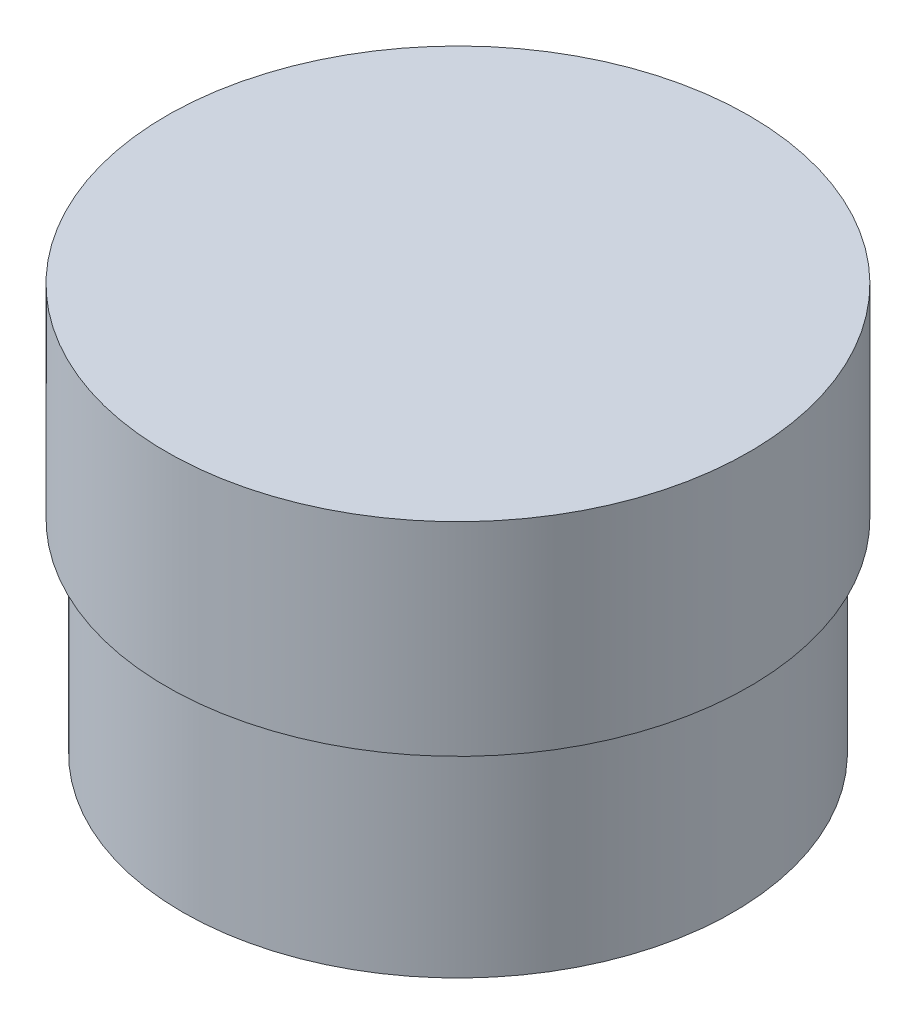
SolidWorks part; units mm, degrees
ref_plane "Front Plane" through (0, 0, 0) normal (0, 0, 1) x (1, 0, 0)
ref_plane "Top Plane" through (0, 0, 0) normal (0, 1, 0) x (1, 0, 0)
ref_plane "Right Plane" through (0, 0, 0) normal (1, 0, 0) x (0, 0, -1)
sketch "Sketch1" plane through (0, 0, 0) normal (0, 1, 0) x (1, 0, 0)
  circle A0 centre (0, 0) radius 28.45
  circle A1 centre (0, 0) radius 30.1
  point P4 (0, 0)
  dimension "D1" = 56.9
  dimension "D2" = 60.2
extrude "Boss-Extrude1" add sketch "Sketch1" along normal blind 21 contours A1
extrude "Boss-Extrude2" add sketch "Sketch1<3>" against normal blind 21 contours A0 region at (0, 0, 0)
sketch "Sketch1<3>" plane through (0, 0, 0) normal (0, 1, 0) x (1, 0, 0) same geometry as "Sketch1"
shell "Shell1" thickness 1 removed face at (0, -21, 28.45)
